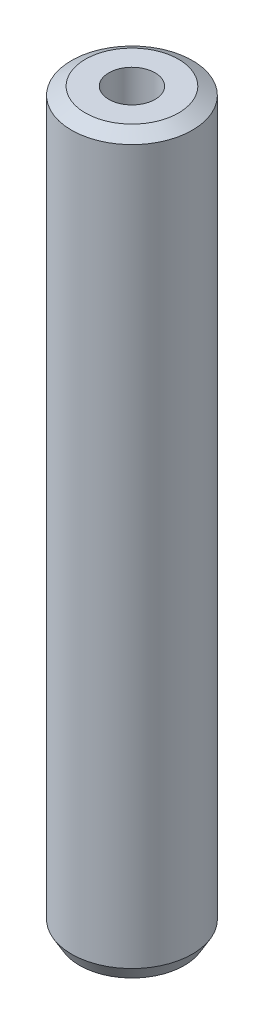
SolidWorks part; units mm, degrees
ref_plane "Front Plane" through (0, 0, 0) normal (0, 0, 1) x (1, 0, 0)
ref_plane "Top Plane" through (0, 0, 0) normal (0, 1, 0) x (1, 0, 0)
ref_plane "Right Plane" through (0, 0, 0) normal (1, 0, 0) x (0, 0, -1)
sketch "Sketch1" plane through (0, 0, 0) normal (0, 1, 0) x (1, 0, 0)
  circle A0 centre (0, 0) radius 12.5
  dimension "SHAFT_OD" = 25
extrude "Boss-Extrude1" add sketch "Sketch1" along normal blind 152.1352
sketch "Sketch2" plane through (0, 0, 0) normal (0, 1, 0) x (1, 0, 0)
  circle A0 centre (0, 0) radius 4.7801
  dimension "BORE_D" = 9.5601
extrude "Cut-Extrude1" cut sketch "Sketch2" along normal through all
chamfer "Chamfer1" distance 1.6526 angle 60 2 edges at (0, 152.1352, 12.5) (0, 0, 12.5) first distance on face at (0, 152.1352, 12.5) first distance on face at (0, 0, 4.7801)
